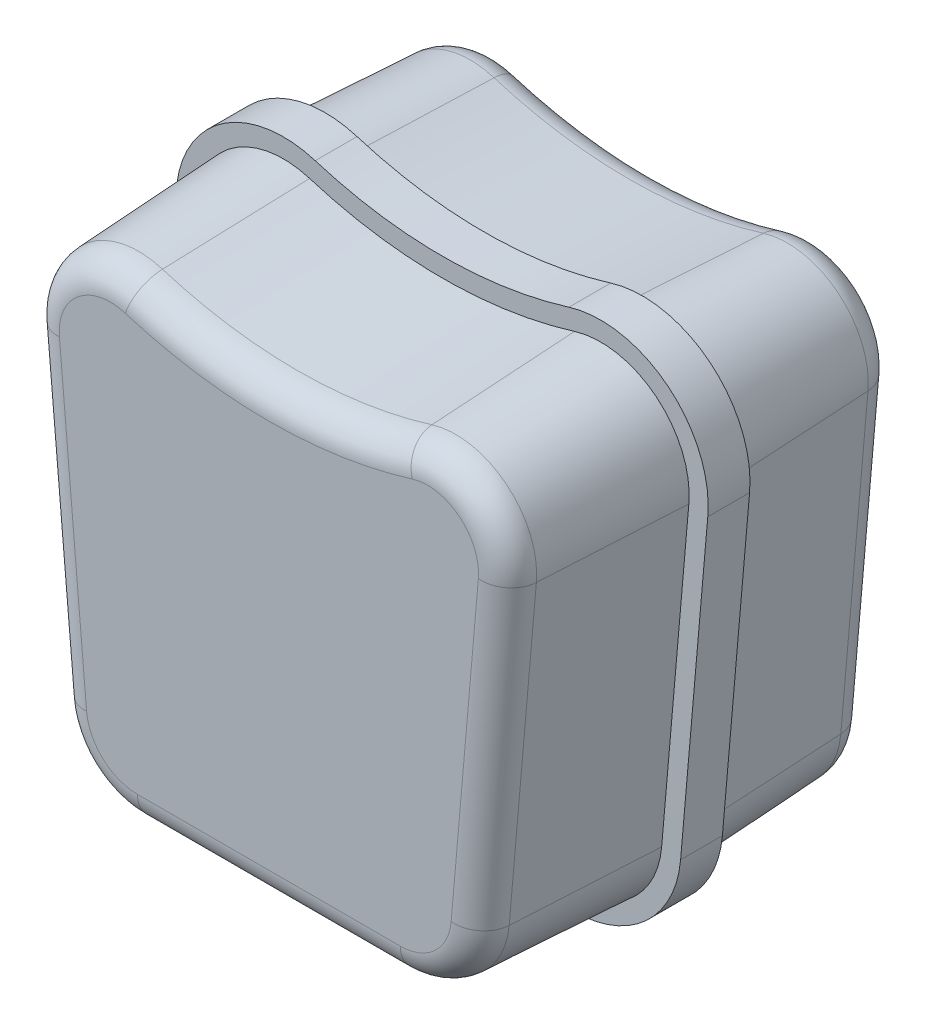
SolidWorks part; units mm, degrees
note: The reader was unsure of these and kept them because the rebuilt part matched: shared geometry of "Sketch1<2>".
ref_plane "Front Plane" through (0, 0, 0) normal (1, 0, 0) x (0, 1, 0)
ref_plane "Top Plane" through (0, 0, 0) normal (0, 0, 1) x (0, 1, 0)
ref_plane "Right Plane" through (0, 0, 0) normal (0, 1, 0) x (-1, 0, 0)
sketch "Sketch1" plane through (0, 0, 0) normal (0, 0, 1) x (0, 1, 0)
  line L0 (-39, -22) -> (-39, 22)
  line L1 (-25.3073, 36.9429) -> (26.6979, 41.4928)
  line L2 (39, 0) -> (-39, 0) construction
  line L3 (-55, 0) -> (55, 0) construction
  line L4 (-25.3073, -36.9429) -> (26.6979, -41.4928)
  arc A0 (-39, 22) -> (-25.3073, 36.9429) centre (-24, 22) cw
  arc A1 (26.6979, 41.4928) -> (42.3377, 22.1249) centre (28.0052, 26.5499) cw
  arc A2 (42.3377, 22.1249) -> (42.3377, -22.1249) centre (114, 0) ccw
  arc A3 (26.6979, -41.4928) -> (42.3377, -22.1249) centre (28.0052, -26.5499) ccw
  arc A4 (-39, -22) -> (-25.3073, -36.9429) centre (-24, -22) ccw
  point P9 (0, 0)
  point P10 (-53.435, 0)
  point P12 (0, 0)
  point P13 (38.0989, 56.3573)
  point P14 (51.7652, 34.2318)
  point P15 (0, 0)
  point P16 (28.2122, 42.1542)
  point P25 (-65.3667, 0)
  point P26 (39, 0)
  point P27 (42.8922, 0)
  dimension "D1" = 75
  dimension "D2" = 15
  dimension "D3" = 5
  dimension "D4" = 78
  dimension "D5" = 22
extrude "Boss-Extrude1" add sketch "Sketch1" along normal mid plane 65 draft 3
fillet "Fillet1" radius 5 16 edges at (30.9832, -33.8034, -32.5) (37.5211, 0.8437, -32.5) (34.9036, 38.3502, -32.5) (0, 37.2967, -32.5) (-30.9832, -33.8034, 32.5) (0, -37.2967, 32.5) (30.9832, -33.8034, 32.5) (37.5211, 0.8437, 32.5) (34.9036, 38.3502, 32.5) (-34.9036, 38.3502, -32.5) (0, 37.2967, 32.5) (-34.9036, 38.3502, 32.5) (-37.5211, 0.8437, 32.5) (-37.5211, 0.8437, -32.5) (-30.9832, -33.8034, -32.5) (0, -37.2967, -32.5)
extrude "Extrude-Thin1" add sketch "Sketch1<2>" along normal mid plane 7 thin thin type mid plane wall 6
sketch "Sketch1<2>" plane through (0, 0, 0) normal (0, 0, 1) x (0, 1, 0) same geometry as "Sketch1"
